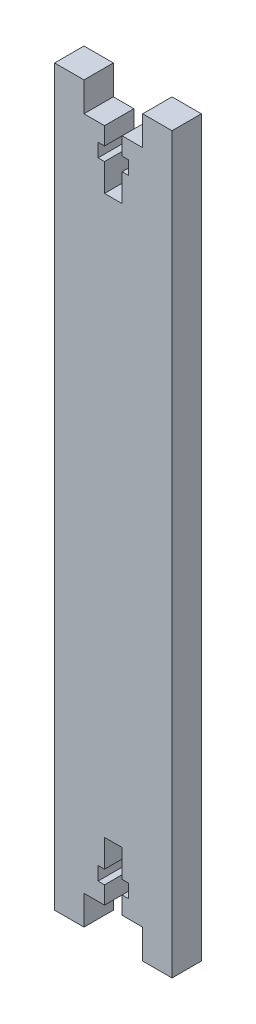
SolidWorks part; units mm, degrees
ref_plane "Front Plane" through (0, 0, 0) normal (0, 0, 1) x (1, 0, 0)
ref_plane "Top Plane" through (0, 0, 0) normal (0, 1, 0) x (1, 0, 0)
ref_plane "Right Plane" through (0, 0, 0) normal (1, 0, 0) x (0, 0, -1)
sketch "Sketch1" plane through (0, 0, 0) normal (0, 0, 1) x (1, 0, 0)
  line L0 (-1.5, 0) -> (-5, 0)
  line L1 (-5, -5) -> (-10, -5)
  line L2 (-10, -5) -> (-10, 0)
  line L3 (-5, -5) -> (-5, 0)
  line L4 (1.5, 0) -> (5, 0)
  line L5 (5, 0) -> (5, -5)
  line L6 (5, -5) -> (10, -5)
  line L7 (10, -5) -> (10, 0)
  line L8 (-1.5, 0) -> (1.5, 0) construction
  line L9 (1.5, 0) -> (1.5, 3)
  line L10 (1.5, 5.3) -> (2.6, 5.3)
  line L11 (-2.6, 3) -> (-2.6, 5.3)
  line L12 (2.6, 3) -> (1.5, 3)
  line L13 (1.5, 5.3) -> (1.5, 10)
  line L14 (1.5, 10) -> (-1.5, 10)
  line L15 (-1.5, 10) -> (-1.5, 5.3)
  line L16 (-1.5, 3) -> (-2.6, 3)
  line L17 (2.6, 5.3) -> (2.6, 3)
  line L18 (-2.6, 5.3) -> (-1.5, 5.3)
  line L19 (-1.5, 3) -> (-1.5, 0)
  line L20 (0, 10) -> (0, 0) construction
  line L21 (-10, 0) -> (-10, 115)
  line L23 (10, 115) -> (10, 0)
  line L24 (0, 105) -> (0, 115) construction
  line L25 (-1.5, 115) -> (1.5, 115) construction
  line L26 (-1.5, 112) -> (-1.5, 115)
  line L27 (-2.6, 109.7) -> (-1.5, 109.7)
  line L28 (2.6, 109.7) -> (2.6, 112)
  line L29 (-1.5, 112) -> (-2.6, 112)
  line L30 (-1.5, 105) -> (-1.5, 109.7)
  line L31 (1.5, 105) -> (-1.5, 105)
  line L32 (1.5, 109.7) -> (1.5, 105)
  line L33 (2.6, 112) -> (1.5, 112)
  line L34 (-2.6, 112) -> (-2.6, 109.7)
  line L35 (1.5, 109.7) -> (2.6, 109.7)
  line L36 (1.5, 115) -> (1.5, 112)
  line L37 (10, 120) -> (10, 115)
  line L38 (5, 120) -> (10, 120)
  line L39 (5, 115) -> (5, 120)
  line L40 (1.5, 115) -> (5, 115)
  line L41 (-5, 120) -> (-5, 115)
  line L42 (-10, 120) -> (-10, 115)
  line L43 (-5, 120) -> (-10, 120)
  line L44 (-1.5, 115) -> (-5, 115)
  line L45 (-10, 57.5) -> (10, 57.5) construction
  dimension "D1" = 5
  dimension "D2" = 5
  dimension "D3" = 5.2
  dimension "D4" = 3
  dimension "D5" = 2.3
  dimension "D6" = 3
  dimension "D7" = 10
  dimension "D8" = 62.5
  dimension "D14" = 10
extrude "Boss-Extrude1" add sketch "Sketch1" along normal blind 5
